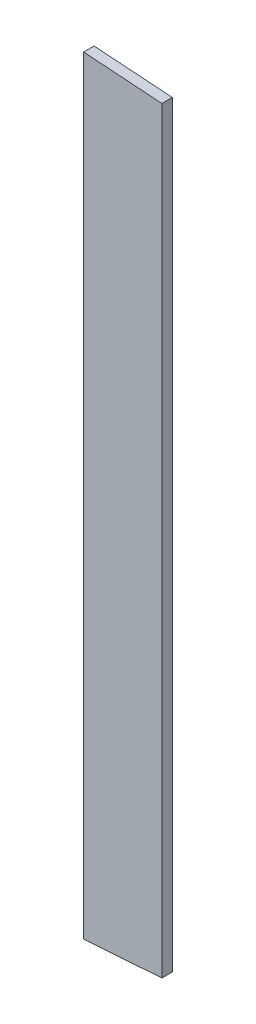
SolidWorks part; units mm, degrees
ref_plane "Front Plane" through (0, 0, 0) normal (0, 0, 1) x (1, 0, 0)
ref_plane "Top Plane" through (0, 0, 0) normal (0, 1, 0) x (1, 0, 0)
ref_plane "Right Plane" through (0, 0, 0) normal (1, 0, 0) x (0, 0, -1)
sketch "Sketch1" plane through (0, 0, 2800.65) normal (0, 0, 1) x (1, 0, 0)
  line L0 (-49.7697, 346.1083) -> (-64.7697, 345.0594)
  line L1 (-140.9262, 339.734) -> (58.5866, 353.6853) construction
  line L2 (-64.7697, 345.0594) -> (-64.7697, 492.4158)
  line L3 (58.5866, 483.7899) -> (-140.9262, 497.7412) construction
  line L4 (-64.7697, 492.4158) -> (-49.7697, 491.3669)
  line L5 (-49.7697, 491.3669) -> (-49.7697, 346.1083)
  dimension "D1" = 15
extrude "Boss-Extrude1" add sketch "Sketch1" along normal blind 2
ref_plane "Plane1" through (-57.2697, 0, 0) normal (1, 0, 0) x (0, 0, -1)
